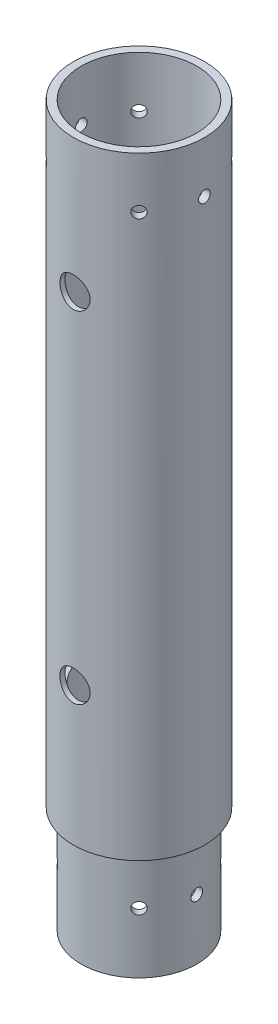
SolidWorks part; units mm, degrees
ref_plane "前视基准面" through (0, 0, 0) normal (0, 0, 1) x (1, 0, 0)
ref_plane "上视基准面" through (0, 0, 0) normal (0, 1, 0) x (1, 0, 0)
ref_plane "右视基准面" through (0, 0, 0) normal (1, 0, 0) x (0, 0, -1)
sketch "草图1" plane through (0, 0, 0) normal (0, 1, 0) x (1, 0, 0)
  circle A0 centre (0, 0) radius 125
  circle A1 centre (0, 0) radius 135
  dimension "D1" = 270
  dimension "D2" = 250
extrude "凸台-拉伸1" add sketch "草图1" along normal blind 1039
sketch "草图10" plane through (0, 0, 0) normal (0, -1, 0) x (-1, 0, 0)
  circle A0 centre (0, 0) radius 105
  circle A1 centre (0, 0) radius 135
  dimension "D1" = 270
  dimension "D2" = 210
extrude "凸台-拉伸2" add sketch "草图10" along normal blind 220
sketch "草图11" plane through (0, -220, 0) normal (0, -1, 0) x (1, 0, 0)
  circle A0 centre (0, 0) radius 105
  circle A1 centre (0, 0) radius 119
  circle A2 centre (0, 0) radius 105 construction
  dimension "D1" = 238
extrude "凸台-拉伸3" add sketch "草图11" along normal blind 220
sketch "草图12" plane through (0, 1039, 0) normal (0, 1, 0) x (1, 0, 0)
  circle A0 centre (0, 0) radius 125
  circle A1 centre (0, 0) radius 119
  dimension "D1" = 250
  dimension "D2" = 238
extrude "凸台-拉伸4" add sketch "草图12" against normal blind 220
ref_axis "基准轴1" through (0, 4914.0051, 0) along (0, -1, 0)
ref_plane "基准面1" through (0, 0, 500) normal (0, 0, 1) x (1, 0, 0)
ref_plane "基准面7" through (-250, 0, 250) normal (0.7071, 0, -0.7071) x (-0.7071, 0, -0.7071)
ref_plane "基准面8" through (250, 0, 250) normal (0.7071, 0, 0.7071) x (0.7071, 0, -0.7071)
ref_plane "基准面10" through (500, 0, 0) normal (1, 0, 0) x (0, 0, -1)
sketch "草图4" plane through (0, 0, 500) normal (0, 0, 1) x (1, 0, 0)
  line L0 (0, 1124) -> (0, 51124) construction
  line L1 (125, 1039) -> (-125, 1039) construction
  circle A0 centre (0, 764) radius 31
  circle A1 centre (0, 64) radius 31
  point P5 (0, 1039)
  dimension "D1" = 62
  dimension "D2" = 275
  dimension "D3" = 700
extrude "切除-拉伸1" cut sketch "草图4" against normal through all
sketch "草图7" plane through (-250, 0, 250) normal (0.7071, 0, -0.7071) x (-0.7071, 0, -0.7071)
  line L0 (0, -1000) -> (0, 49000) construction
  line L2 (125, 1039) -> (-125, 1039) construction
  circle A0 centre (0, 934) radius 12
  dimension "D1" = 24
  dimension "D2" = 105
extrude "切除-拉伸3" cut sketch "草图7" along normal through all
sketch "草图8" plane through (250, 0, 250) normal (0.7071, 0, 0.7071) x (0.7071, 0, -0.7071)
  line L0 (0, -1000) -> (0, 49000) construction
  line L2 (125, 1039) -> (-125, 1039) construction
  circle A0 centre (0, 934) radius 12
  dimension "D2" = 24
  dimension "D1" = 105
extrude "切除-拉伸4" cut sketch "草图8" against normal through all
sketch "草图9" plane through (500, 0, 0) normal (1, 0, 0) x (0, 0, -1)
  line L0 (0, -1000) -> (0, 49000) construction
  line L3 (135, 1039) -> (-135, 1039) construction
  circle A0 centre (0, 934) radius 12
  dimension "D2" = 24
  dimension "D1" = 105
extrude "切除-拉伸5" cut sketch "草图9" against normal through all
pattern_linear "阵列(线性)1" count 2 spacing 1250 along (0, -1, 0) of "切除-拉伸4", "切除-拉伸3", "切除-拉伸5"
